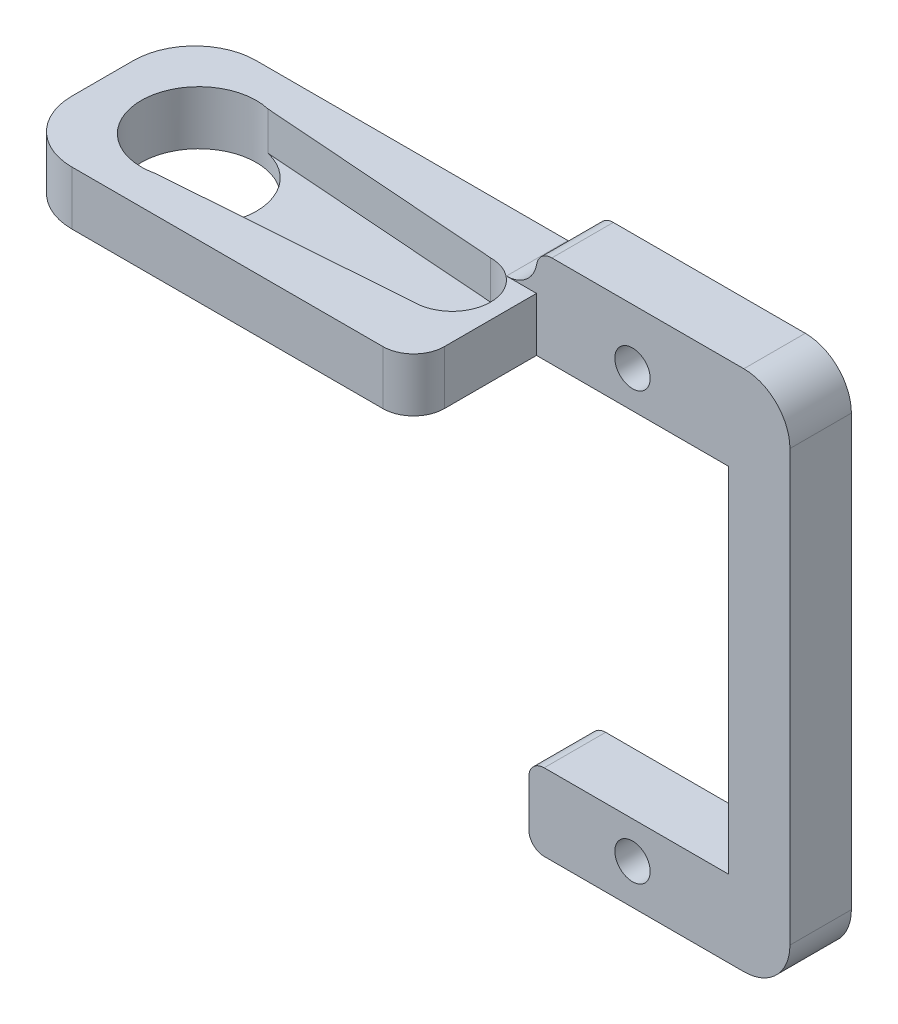
SolidWorks part; units mm, degrees
ref_plane "Front Plane" through (0, 0, 0) normal (0, 0, 1) x (1, 0, 0)
ref_plane "Top Plane" through (0, 0, 0) normal (0, 1, 0) x (1, 0, 0)
ref_plane "Right Plane" through (0, 0, 0) normal (1, 0, 0) x (0, 0, -1)
sketch "Sketch1" plane through (0, 0, 0) normal (0, 1, 0) x (1, 0, 0)
  line L0 (-11.375, 0) -> (-11.375, -10.3958) construction
  line L1 (-12.375, 6) -> (12.375, 6)
  line L2 (-12.375, 6) -> (-12.375, -6)
  line L3 (-12.375, -6) -> (12.375, -6)
  line L4 (12.375, 6) -> (12.375, -6)
  line L5 (-12.375, 6) -> (12.375, -6) construction
  line L6 (-12.375, -6) -> (12.375, 6) construction
  line L7 (11.375, 0) -> (11.375, -4.6491) construction
  line L8 (8.875, 2.5) -> (-6.7648, 3.65)
  line L9 (8.875, -2.5) -> (-6.7648, -3.65)
  circle A0 centre (-7.625, 0) radius 3.75
  arc A1 (8.875, -2.5) -> (8.875, 2.5) centre (8.875, 0) ccw
  point P0 (0, 0)
  dimension "D3" = 7.5
  dimension "D4" = 6
  dimension "D6" = 5
  dimension "D7" = 6
  dimension "D8" = 19
  dimension "D1" = 12
  dimension "D2" = 24.75
  dimension "D5" = 1
  dimension "D9" = 4.3958
  dimension "D10" = 1.3509
  dimension "D11" = 7.3
extrude "Boss-Extrude1" add sketch "Sketch1" along normal blind 3.5 contours L4 L1 L2 L3 A1 L9 A0 L8 | A0 | L9 A1 L8 A0 region at (0, 0, -5.7249) region at (2.651, 0, 0) region at (-7.625, 0, 0)
sketch "Sketch2" plane through (0, 3.5, 0) normal (0, 1, 0) x (1, 0, 0)
  line L0 (11.375, 0.0094) -> (11.375, -2.6086) construction
  line L1 (8.875, 2.5094) -> (-6.7648, 3.6594)
  line L2 (8.875, -2.4906) -> (-6.7648, -3.6406)
  line L3 (-7.625, 0.0094) -> (9.375, 0.0094) construction
  line L4 (12.375, 6) -> (12.375, -6) construction
  line L5 (-12.375, 6) -> (12.375, 6) construction
  line L6 (-11.375, 0.0094) -> (-11.375, -3.4601) construction
  circle A0 centre (-7.625, 0.0094) radius 3.75
  arc A1 (8.875, -2.4906) -> (8.875, 2.5094) centre (8.875, 0.0094) ccw
  point P0 (0.0859, 0.0094)
  dimension "D4" = 7.5
  dimension "D5" = 5.9906
  dimension "D6" = 19
  dimension "D7" = 2.5
  dimension "D8" = 1
  dimension "D1" = 7.3
extrude "Cut-Extrude1" cut sketch "Sketch2" against normal through all contours A0 region at (-7.625, 3.5, -0.0094)
sketch "Sketch4" plane through (0, 3.5, 0) normal (0, 1, 0) x (1, 0, 0)
  line L0 (-6.7648, 3.6594) -> (8.875, 2.5094)
  line L1 (-6.7648, -3.6406) -> (8.875, -2.4906)
  line L2 (-7.625, 0.0094) -> (9.375, 0.0094) construction
  arc A0 (8.875, -2.4906) -> (8.875, 2.5094) centre (8.875, 0.0094) ccw
  arc A6 (-6.7648, 3.6594) -> (-6.7648, -3.6406) centre (-7.625, 0.0094) cw
  dimension "D4" = 3.75
extrude "Cut-Extrude4" cut sketch "Sketch4" against normal blind 2.5
sketch "Sketch5" plane through (12.375, 0, 0) normal (1, 0, 0) x (0, 0, -1)
  line L0 (6, 3.5) -> (-6, 3.5) construction
  line L1 (2, 3.5) -> (6, 3.5)
  line L2 (2, 3.5) -> (2, 0)
  line L3 (2, 0) -> (6, 0)
  line L4 (6, 3.5) -> (6, 0)
  dimension "D1" = 4
extrude "Boss-Extrude2" add sketch "Sketch5" along normal blind 12.5
sketch "Sketch6" plane through (24.875, 0, 0) normal (1, 0, 0) x (0, 0, -1)
  line L0 (6, 0) -> (6, 3.5) construction
  line L1 (2, 3.5) -> (6, 3.5)
  line L2 (2, 3.5) -> (2, 0)
  line L3 (2, 0) -> (6, 0)
  line L4 (6, 3.5) -> (6, 0)
  line L5 (2, 0) -> (6, 0) construction
extrude "Boss-Extrude3" add sketch "Sketch6" along normal blind 4
sketch "Sketch7" plane through (0, 0, 0) normal (0, -1, 0) x (1, 0, 0)
  line L0 (-12.375, -6) -> (28.875, -6) construction
  line L1 (28.875, -2) -> (24.875, -2)
  line L2 (28.875, -2) -> (28.875, -6)
  line L3 (28.875, -6) -> (24.875, -6)
  line L4 (24.875, -2) -> (24.875, -6)
  dimension "D1" = 4
extrude "Boss-Extrude4" add sketch "Sketch7" along normal blind 28
sketch "Sketch8" plane through (24.875, 0, 0) normal (-1, 0, 0) x (0, 0, 1)
  line L0 (-2, -28) -> (-2, 0) construction
  line L1 (-6, -28) -> (-2, -28)
  line L2 (-6, -28) -> (-6, -23)
  line L3 (-6, -23) -> (-2, -23)
  line L4 (-2, -28) -> (-2, -23)
  dimension "D1" = 5
extrude "Boss-Extrude5" add sketch "Sketch8" along normal blind 13
sketch "Sketch9" plane through (0, 3.5, 0) normal (0, 1, 0) x (1, 0, 0)
  line L1 (12.375, 2) -> (28.875, 2)
  line L2 (12.375, 2) -> (12.375, 6)
  line L3 (12.375, 6) -> (28.875, 6)
  line L4 (28.875, 2) -> (28.875, 6)
extrude "Boss-Extrude6" add sketch "Sketch9" along normal blind 2.5
sketch "Sketch10" plane through (0, 0, -2) normal (0, 0, 1) x (1, 0, 0)
  line L0 (24.875, 0) -> (12.375, 0) construction
  line L2 (28.875, 6) -> (28.875, -28) construction
  line L3 (11.875, -23) -> (24.875, -23) construction
  circle A0 centre (18.625, 2.4) radius 1.15
  circle A1 centre (18.625, -25.4) radius 1.15
  dimension "D2" = 2.3
  dimension "D3" = 10.25
  dimension "D4" = 2.3
  dimension "D5" = 2.4
  dimension "D6" = 10.25
  dimension "D1" = 2.4
extrude "Cut-Extrude5" cut sketch "Sketch10" along normal through all and the other way blind 50
fillet "Fillet4" radius 1 3 edges at (11.875, -28, -4) (11.875, -23, -4) (12.375, 6, -4)
sketch "Sketch13" plane through (-12.375, 0, 0) normal (-1, 0, 0) x (0, 0, 1)
  line L1 (-6, 3.5) -> (6, 3.5)
  line L2 (-6, 3.5) -> (-6, 0)
  line L3 (-6, 0) -> (6, 0)
  line L4 (6, 3.5) -> (6, 0)
  line M1 (-6, 0) -> (6, 0)
  line M2 (6, 0) -> (6, 3.5)
  line M3 (6, 3.5) -> (-6, 3.5)
  line M4 (-6, 3.5) -> (-6, 0)
extrude "Boss-Extrude7" add sketch "Sketch13" along normal blind 1.5 contours M4 M1 M2 M3 region at (-12.375, 1.75, 0)
fillet "Fillet5" radius 4 1 edges at (-13.875, 1.75, 6)
fillet "Fillet6" radius 4 1 edges at (-13.875, 1.75, -6)
fillet "Fillet7" radius 2 1 edges at (12.375, 1.75, 6)
fillet "Fillet8" radius 3 2 edges at (28.875, -28, -4) (28.875, 6, -4)
fillet "Fillet9" radius 2 1 edges at (12.375, 3.5, -4)
